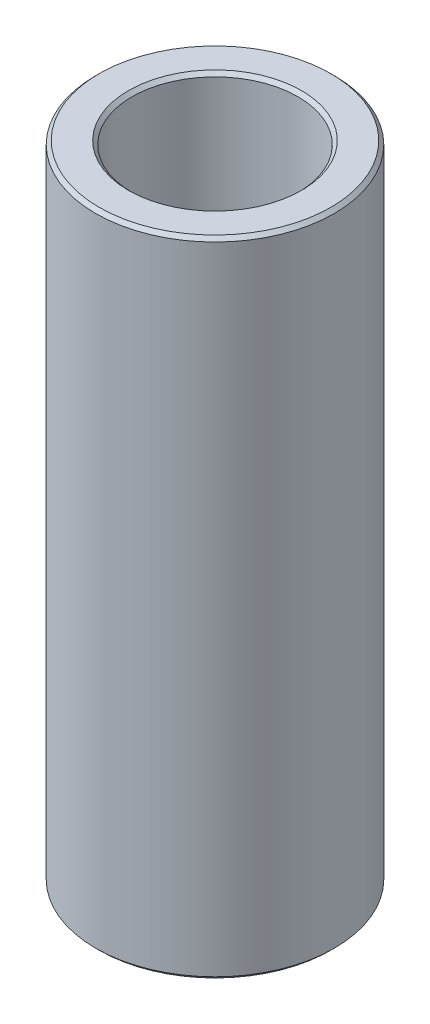
SolidWorks part; units mm, degrees
ref_plane "Front Plane" through (0, 0, 0) normal (0, 0, 1) x (1, 0, 0)
ref_plane "Top Plane" through (0, 0, 0) normal (0, 1, 0) x (1, 0, 0)
ref_plane "Right Plane" through (0, 0, 0) normal (1, 0, 0) x (0, 0, -1)
sketch "Sketch1" plane through (0, 0, 0) normal (0, 1, 0) x (1, 0, 0)
  circle A0 centre (0, 0) radius 15
  dimension "SLEEVE_OD" = 30
extrude "Boss-Extrude1" add sketch "Sketch1" along normal blind 80.8551
sketch "Sketch2" plane through (0, 0, 0) normal (0, 1, 0) x (1, 0, 0)
  circle A0 centre (0, 0) radius 10.4262
  dimension "BORE_D" = 20.8524
extrude "Cut-Extrude1" cut sketch "Sketch2" along normal through all
chamfer "Chamfer1" distance 0.4456 angle 45 4 edges at (0, 80.8551, 10.4262) (0, 0, 10.4262) (0, 0, 15) (0, 80.8551, 15)
